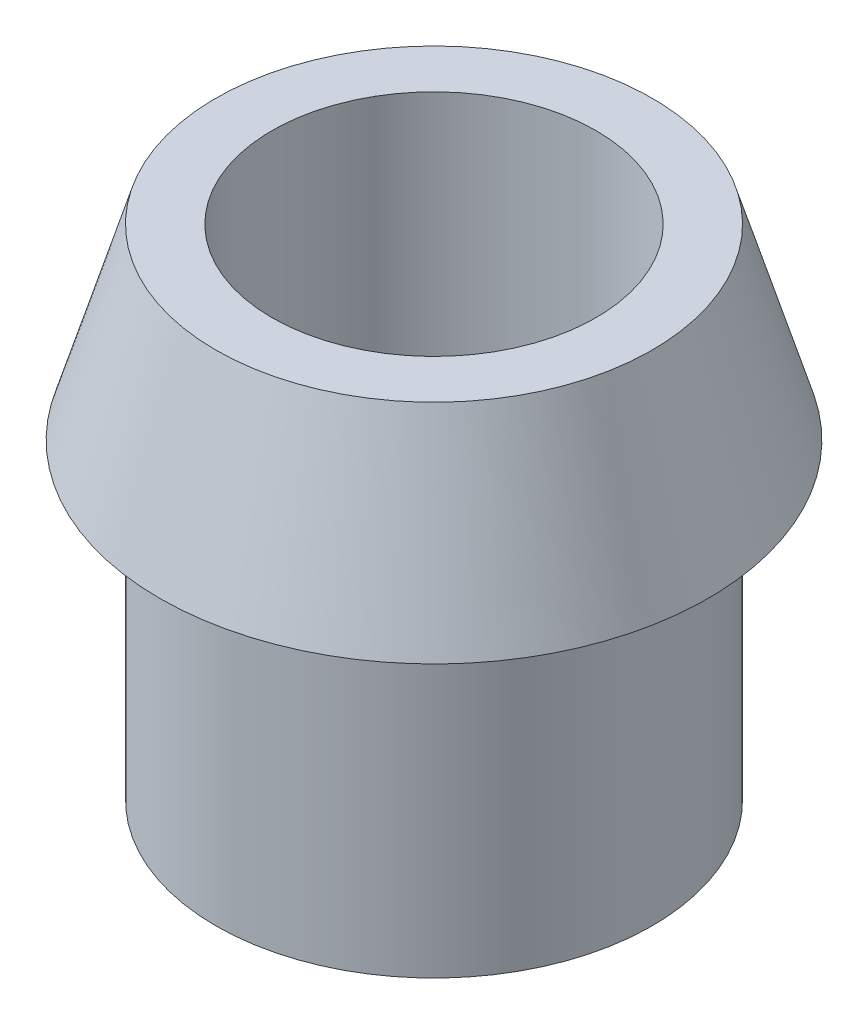
SolidWorks part; units mm, degrees
ref_plane "Front Plane" through (0, 0, 0) normal (0, 0, 1) x (1, 0, 0)
ref_plane "Top Plane" through (0, 0, 0) normal (0, 1, 0) x (1, 0, 0)
ref_plane "Right Plane" through (0, 0, 0) normal (1, 0, 0) x (0, 0, -1)
sketch "Sketch1" plane through (0, 0, 0) normal (0, 1, 0) x (1, 0, 0)
  circle A0 centre (0, 0) radius 3.5
extrude "Boss-Extrude1" add sketch "Sketch1" along normal blind 5
sketch "Sketch2" plane through (0, 5, 0) normal (0, 1, 0) x (1, 0, 0)
  circle A0 centre (0, 0) radius 5
extrude "Boss-Extrude2" add sketch "Sketch2" along normal blind 3
chamfer "Chamfer1" distance 5 distance2 1.5 1 edges at (0, 8, 5) first distance on face at (0, 8, 5)
sketch "Sketch3" plane through (0, 8, 0) normal (0, 1, 0) x (1, 0, 0)
  circle A0 centre (0, 0) radius 2.6
extrude "Cut-Extrude1" cut sketch "Sketch3" against normal blind 20
